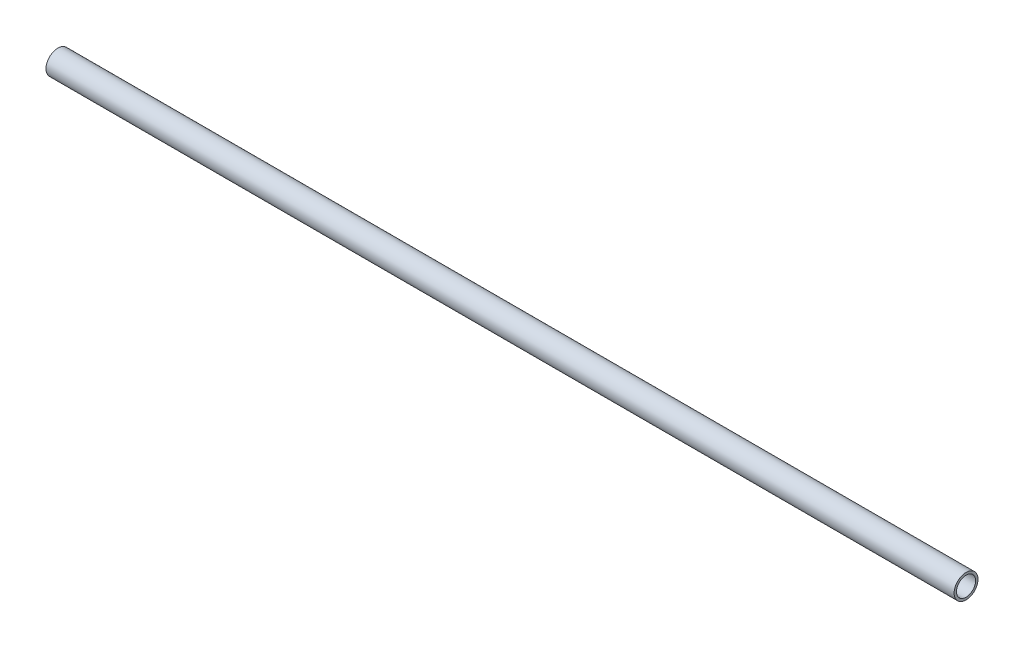
SolidWorks part; units mm, degrees
ref_plane "Front Plane" through (0, 0, 0) normal (0, 0, 1) x (1, 0, 0)
ref_plane "Top Plane" through (0, 0, 0) normal (0, 1, 0) x (1, 0, 0)
ref_plane "Right Plane" through (0, 0, 0) normal (1, 0, 0) x (0, 0, -1)
sketch "Sketch1" plane through (0, 0, 0) normal (0, 1, 0) x (1, 0, 0)
  line L0 (0, 0) -> (640, 0) construction
  line L1 (0, 0) -> (591.2829, 244.9174)
  line L2 (0, 0) -> (591.2829, -244.9174)
  line L3 (0, 0) -> (244.9174, -591.2829)
  line L4 (0, 0) -> (-244.9174, -591.2829)
  line L5 (0, 0) -> (-591.2829, -244.9174)
  line L6 (0, 0) -> (-591.2829, 244.9174)
  line L7 (0, 0) -> (-244.9174, 591.2829)
  line L8 (0, 0) -> (244.9174, 591.2829)
  line L9 (0, 145) -> (55, 145) construction
  line L10 (0, 0) -> (100, 0) construction
  line L11 (0, 0) -> (0, 145) construction
  line L14 (100, 0) -> (100, 145) construction
  circle A0 centre (0, 0) radius 640 construction
  point P15 (0, 0)
  dimension "D1" = 1280
  dimension "D2" = 22.5
  dimension "D4" = 145
  dimension "D5" = 100
  dimension "D6" = 55
  dimension "D3" = 8
sketch "Sketch2" plane through (0, 0, 0) normal (0, 1, 0) x (1, 0, 0)
  line L0 (-486.9956, 169.5033) -> (-66.9956, 169.5033) construction
  line L1 (-188.7141, -86.1278) -> (-188.7141, 241.8722) construction
  line L2 (525.6625, -1048.8053) -> (466.9027, -726.1115) construction
sketch "Sketch3" plane through (0, 0, 0) normal (0, 1, 0) x (1, 0, 0)
  line L0 (0, 0) -> (381.2468, 0) construction
  line L5 (0, 0) -> (0, 199.4415) construction
  line L6 (-10.2736, 158.9263) -> (10.2736, 158.9263)
  line L7 (10.2736, 158.9263) -> (13.1995, 163.9003)
  line L8 (13.1995, 163.9003) -> (45.5131, 148.2994)
  line L9 (45.5131, 148.2994) -> (66.2904, 80.9335)
  line L10 (66.2904, 80.9335) -> (73.8622, 80.9335)
  line L11 (73.8622, 80.9335) -> (86.8684, 42.4396)
  line L12 (86.8684, 42.4396) -> (86.8684, 30.0712)
  line L13 (86.8684, 30.0712) -> (81.3965, 24.5993)
  line L14 (81.3965, 24.5993) -> (81.3965, -24.5993)
  line L15 (-5.8349, 67.4929) -> (5.8349, 67.4929) construction
  line L16 (16.6008, 64.1674) -> (16.6008, 27.6557) construction
  line L17 (16.6008, 27.6557) -> (13.2646, 22.809) construction
  line L18 (13.2646, 22.809) -> (13.2646, -22.809) construction
  line L19 (5.8349, 128.0146) -> (5.8349, 107.4452)
  line L22 (5.8349, 107.4452) -> (9.2702, 107.4452)
  line L25 (9.2702, 107.4452) -> (10.663, 103.7163)
  line L26 (10.663, 103.7163) -> (20.7578, 101.0699)
  line L27 (20.7578, 101.0699) -> (32.199, 111.7601)
  line L28 (32.199, 111.7601) -> (32.199, 123.5038)
  line L29 (32.199, 123.5038) -> (24.9078, 123.5038)
  line L30 (24.9078, 123.5038) -> (13.8412, 132.5856)
  line L31 (13.8412, 132.5856) -> (9.2702, 132.5856)
  line L32 (9.2702, 132.5856) -> (5.8349, 128.0146)
  line L33 (41.9414, 39.7891) -> (51.4866, 54.1602)
  line L34 (51.4866, 54.1602) -> (55.4027, 54.1602)
  line L35 (55.4027, 54.1602) -> (58.1637, 51.3993)
  line L36 (58.1637, 51.3993) -> (58.1637, 43.1872)
  line L37 (58.1637, 43.1872) -> (66.3555, 28.462)
  line L38 (66.3555, 28.462) -> (66.3555, 24.0728)
  line L39 (66.3555, 24.0728) -> (62.2596, 17.9061)
  line L40 (62.2596, 17.9061) -> (47.8497, 18.1669)
  line L41 (47.8497, 18.1669) -> (41.9414, 27.1878)
  line L42 (41.9414, 27.1878) -> (41.9414, 39.7891)
  line L43 (-41.9414, 27.1878) -> (-41.9414, 39.7891)
  line L44 (-47.8497, 18.1669) -> (-41.9414, 27.1878)
  line L45 (-62.2596, 17.9061) -> (-47.8497, 18.1669)
  line L46 (-66.3555, 24.0728) -> (-62.2596, 17.9061)
  line L47 (-66.3555, 28.462) -> (-66.3555, 24.0728)
  line L48 (-58.1637, 43.1872) -> (-66.3555, 28.462)
  line L49 (-58.1637, 51.3993) -> (-58.1637, 43.1872)
  line L50 (-55.4027, 54.1602) -> (-58.1637, 51.3993)
  line L51 (-51.4866, 54.1602) -> (-55.4027, 54.1602)
  line L52 (-41.9414, 39.7891) -> (-51.4866, 54.1602)
  line L53 (-9.2702, 132.5856) -> (-5.8349, 128.0146)
  line L54 (-13.8412, 132.5856) -> (-9.2702, 132.5856)
  line L55 (-24.9078, 123.5038) -> (-13.8412, 132.5856)
  line L56 (-32.199, 123.5038) -> (-24.9078, 123.5038)
  line L57 (-32.199, 111.7601) -> (-32.199, 123.5038)
  line L58 (-20.7578, 101.0699) -> (-32.199, 111.7601)
  line L59 (-10.663, 103.7163) -> (-20.7578, 101.0699)
  line L60 (-9.2702, 107.4452) -> (-10.663, 103.7163)
  line L61 (-5.8349, 107.4452) -> (-9.2702, 107.4452)
  line L62 (-5.8349, 128.0146) -> (-5.8349, 107.4452)
  line L63 (-13.2646, 22.809) -> (-13.2646, -22.809) construction
  line L64 (-16.6008, 27.6557) -> (-13.2646, 22.809) construction
  line L65 (-16.6008, 64.1674) -> (-16.6008, 27.6557) construction
  line L66 (-81.3965, 24.5993) -> (-81.3965, -24.5993)
  line L67 (-86.8684, 30.0712) -> (-81.3965, 24.5993)
  line L68 (-86.8684, 42.4396) -> (-86.8684, 30.0712)
  line L69 (-73.8622, 80.9335) -> (-86.8684, 42.4396)
  line L70 (-66.2904, 80.9335) -> (-73.8622, 80.9335)
  line L71 (-45.5131, 148.2994) -> (-66.2904, 80.9335)
  line L72 (-13.1995, 163.9003) -> (-45.5131, 148.2994)
  line L73 (-10.2736, 158.9263) -> (-13.1995, 163.9003)
  line L74 (-10.2736, -158.9263) -> (-13.1995, -163.9003)
  line L75 (-13.1995, -163.9003) -> (-45.5131, -148.2994)
  line L76 (-45.5131, -148.2994) -> (-66.2904, -80.9335)
  line L77 (-66.2904, -80.9335) -> (-73.8622, -80.9335)
  line L78 (-73.8622, -80.9335) -> (-86.8684, -42.4396)
  line L79 (-86.8684, -42.4396) -> (-86.8684, -30.0712)
  line L80 (-86.8684, -30.0712) -> (-81.3965, -24.5993)
  line L81 (-16.6008, -64.1674) -> (-16.6008, -27.6557) construction
  line L82 (-16.6008, -27.6557) -> (-13.2646, -22.809) construction
  line L83 (-5.8349, -128.0146) -> (-5.8349, -107.4452)
  line L84 (-5.8349, -107.4452) -> (-9.2702, -107.4452)
  line L85 (-9.2702, -107.4452) -> (-10.663, -103.7163)
  line L86 (-10.663, -103.7163) -> (-20.7578, -101.0699)
  line L87 (-20.7578, -101.0699) -> (-32.199, -111.7601)
  line L88 (-32.199, -111.7601) -> (-32.199, -123.5038)
  line L89 (-32.199, -123.5038) -> (-24.9078, -123.5038)
  line L90 (-24.9078, -123.5038) -> (-13.8412, -132.5856)
  line L91 (-13.8412, -132.5856) -> (-9.2702, -132.5856)
  line L92 (-9.2702, -132.5856) -> (-5.8349, -128.0146)
  line L93 (-41.9414, -39.7891) -> (-51.4866, -54.1602)
  line L94 (-51.4866, -54.1602) -> (-55.4027, -54.1602)
  line L95 (-55.4027, -54.1602) -> (-58.1637, -51.3993)
  line L96 (-58.1637, -51.3993) -> (-58.1637, -43.1872)
  line L97 (-58.1637, -43.1872) -> (-66.3555, -28.462)
  line L98 (-66.3555, -28.462) -> (-66.3555, -24.0728)
  line L99 (-66.3555, -24.0728) -> (-62.2596, -17.9061)
  line L100 (-62.2596, -17.9061) -> (-47.8497, -18.1669)
  line L101 (-47.8497, -18.1669) -> (-41.9414, -27.1878)
  line L102 (-41.9414, -27.1878) -> (-41.9414, -39.7891)
  line L103 (41.9414, -27.1878) -> (41.9414, -39.7891)
  line L104 (47.8497, -18.1669) -> (41.9414, -27.1878)
  line L105 (62.2596, -17.9061) -> (47.8497, -18.1669)
  line L106 (66.3555, -24.0728) -> (62.2596, -17.9061)
  line L107 (66.3555, -28.462) -> (66.3555, -24.0728)
  line L108 (58.1637, -43.1872) -> (66.3555, -28.462)
  line L109 (58.1637, -51.3993) -> (58.1637, -43.1872)
  line L110 (55.4027, -54.1602) -> (58.1637, -51.3993)
  line L111 (51.4866, -54.1602) -> (55.4027, -54.1602)
  line L112 (41.9414, -39.7891) -> (51.4866, -54.1602)
  line L113 (9.2702, -132.5856) -> (5.8349, -128.0146)
  line L114 (13.8412, -132.5856) -> (9.2702, -132.5856)
  line L115 (24.9078, -123.5038) -> (13.8412, -132.5856)
  line L116 (32.199, -123.5038) -> (24.9078, -123.5038)
  line L117 (32.199, -111.7601) -> (32.199, -123.5038)
  line L118 (20.7578, -101.0699) -> (32.199, -111.7601)
  line L119 (10.663, -103.7163) -> (20.7578, -101.0699)
  line L120 (9.2702, -107.4452) -> (10.663, -103.7163)
  line L121 (5.8349, -107.4452) -> (9.2702, -107.4452)
  line L122 (5.8349, -128.0146) -> (5.8349, -107.4452)
  line L123 (16.6008, -27.6557) -> (13.2646, -22.809) construction
  line L124 (16.6008, -64.1674) -> (16.6008, -27.6557) construction
  line L125 (-5.8349, -67.4929) -> (5.8349, -67.4929) construction
  line L126 (86.8684, -30.0712) -> (81.3965, -24.5993)
  line L127 (86.8684, -42.4396) -> (86.8684, -30.0712)
  line L128 (73.8622, -80.9335) -> (86.8684, -42.4396)
  line L129 (66.2904, -80.9335) -> (73.8622, -80.9335)
  line L130 (45.5131, -148.2994) -> (66.2904, -80.9335)
  line L131 (13.1995, -163.9003) -> (45.5131, -148.2994)
  line L132 (10.2736, -158.9263) -> (13.1995, -163.9003)
  line L133 (-10.2736, -158.9263) -> (10.2736, -158.9263)
  line L134 (-5.3457, 68.4929) -> (5.3457, 68.4929)
  line L135 (17.6008, 64.1674) -> (17.6008, 27.3448)
  line L136 (17.6008, 27.3448) -> (14.2646, 22.498)
  line L137 (14.2646, 22.498) -> (14.2646, -22.498)
  line L138 (-17.6008, 64.1674) -> (-17.6008, 27.3448)
  line L139 (-17.6008, 27.3448) -> (-14.2646, 22.498)
  line L140 (-5.3457, 68.4929) -> (5.3457, 68.4929) construction
  line L141 (14.2646, 22.498) -> (14.2646, -22.498) construction
  line L142 (17.6008, -27.3448) -> (14.2646, -22.498) construction
  line L143 (17.6008, -64.1674) -> (17.6008, -27.3448) construction
  line L144 (-14.2646, 22.498) -> (-14.2646, -22.498)
  line L145 (17.6008, -64.1674) -> (17.6008, -27.3448)
  line L146 (17.6008, -27.3448) -> (14.2646, -22.498)
  line L147 (-17.6008, -27.3448) -> (-14.2646, -22.498)
  line L148 (-17.6008, -64.1674) -> (-17.6008, -27.3448)
  line L149 (-5.3457, -68.4929) -> (5.3457, -68.4929)
  arc A0 (5.8349, 67.4929) -> (16.6008, 64.0252) centre (10.663, 64.0364) cw construction
  arc A5 (-5.8349, 67.4929) -> (-16.6008, 64.0252) centre (-10.663, 64.0364) ccw construction
  arc A6 (-5.8349, -67.4929) -> (-16.6008, -64.0252) centre (-10.663, -64.0364) cw construction
  arc A7 (5.8349, -67.4929) -> (16.6008, -64.0252) centre (10.663, -64.0364) ccw construction
  arc A8 (-5.3457, 68.4929) -> (-17.6008, 64.0234) centre (-10.663, 64.0364) ccw
  arc A9 (5.3457, 68.4929) -> (17.6008, 64.0234) centre (10.663, 64.0364) cw
  arc A10 (-5.3457, 68.4929) -> (-17.6008, 64.0234) centre (-10.663, 64.0364) ccw construction
  arc A11 (5.3457, -68.4929) -> (17.6008, -64.0234) centre (10.663, -64.0364) ccw
  arc A12 (-5.3457, -68.4929) -> (-17.6008, -64.0234) centre (-10.663, -64.0364) cw
  ellipse E0 centre (11.3851, 149.6854) end of major axis (12.0553, 155.2702) minor radius 3.0047
  ellipse E1 centre (33.6925, 82.363) end of major axis (41.1096, 88.3895) minor radius 4.3287
  ellipse E2 centre (44.8955, 74.0187) end of major axis (51.4866, 79.374) minor radius 4.6847
  ellipse E3 centre (66.3555, 66.447) end of major axis (67.1471, 72.2416) minor radius 3.5711
  ellipse E4 centre (-66.3555, 66.447) end of major axis (-67.1471, 72.2416) minor radius 3.5711
  ellipse E5 centre (-44.8955, 74.0187) end of major axis (-51.4866, 79.374) minor radius 4.6847
  ellipse E6 centre (-33.6925, 82.363) end of major axis (-41.1096, 88.3895) minor radius 4.3287
  ellipse E7 centre (-11.3851, 149.6854) end of major axis (-12.0553, 155.2702) minor radius 3.0047
  ellipse E8 centre (-11.3851, -149.6854) end of major axis (-12.0553, -155.2702) minor radius 3.0047
  ellipse E9 centre (-33.6925, -82.363) end of major axis (-41.1096, -88.3895) minor radius 4.3287
  ellipse E10 centre (-44.8955, -74.0187) end of major axis (-51.4866, -79.374) minor radius 4.6847
  ellipse E11 centre (-66.3555, -66.447) end of major axis (-67.1471, -72.2416) minor radius 3.5711
  ellipse E12 centre (66.3555, -66.447) end of major axis (67.1471, -72.2416) minor radius 3.5711
  ellipse E13 centre (44.8955, -74.0187) end of major axis (51.4866, -79.374) minor radius 4.6847
  ellipse E14 centre (33.6925, -82.363) end of major axis (41.1096, -88.3895) minor radius 4.3287
  ellipse E15 centre (11.3851, -149.6854) end of major axis (12.0553, -155.2702) minor radius 3.0047
  point P117 (0, 67.4929)
  point P126 (0, 158.9263)
  point P180 (0, -158.9263)
  point P181 (0, -67.4929)
  point P190 (-81.3965, 0)
  point P193 (-13.2646, 0)
  point P234 (13.2646, 0)
  point P237 (81.3965, 0)
  point P261 (0, 68.4929)
  point P271 (14.2646, 0)
  point P274 (-14.2646, 0)
  dimension "D1" = 1
sketch "Sketch4" plane through (0, 0, 0) normal (0, 1, 0) x (1, 0, 0)
  line L0 (0, 0) -> (81.2255, 0) construction
  line L1 (0, 0) -> (0, 97.3086) construction
  line L2 (0, 0) -> (0, 199.4415) construction
  line L3 (-10.1399, 86.6928) -> (10.1399, 86.6928)
  line L4 (10.1399, 86.6928) -> (16.0235, 80.8091)
  line L5 (16.0235, 80.8091) -> (23.9736, 57.3032)
  line L6 (23.9736, 57.3032) -> (23.9736, 47.8894)
  line L7 (23.9736, 47.8894) -> (21.6776, 47.8894)
  line L8 (21.6776, 47.8894) -> (21.6776, 27.2256)
  line L9 (21.6776, 27.2256) -> (27.5382, 22.1416)
  line L10 (27.5382, 22.1416) -> (27.5382, 14.9676)
  line L11 (27.5382, 14.9676) -> (23.9736, 10.8585)
  line L12 (23.9736, 10.8585) -> (23.9736, -10.8585)
  line L13 (-23.9736, 10.8585) -> (-23.9736, -10.8585)
  line L14 (-27.5382, 14.9676) -> (-23.9736, 10.8585)
  line L15 (-27.5382, 22.1416) -> (-27.5382, 14.9676)
  line L16 (-21.6776, 27.2256) -> (-27.5382, 22.1416)
  line L17 (-21.6776, 47.8894) -> (-21.6776, 27.2256)
  line L18 (-23.9736, 47.8894) -> (-21.6776, 47.8894)
  line L19 (-23.9736, 57.3032) -> (-23.9736, 47.8894)
  line L20 (-16.0235, 80.8091) -> (-23.9736, 57.3032)
  line L21 (-10.1399, 86.6928) -> (-16.0235, 80.8091)
  line L22 (-10.1399, -86.6928) -> (-16.0235, -80.8091)
  line L23 (-16.0235, -80.8091) -> (-23.9736, -57.3032)
  line L24 (-23.9736, -57.3032) -> (-23.9736, -47.8894)
  line L25 (-23.9736, -47.8894) -> (-21.6776, -47.8894)
  line L26 (-21.6776, -47.8894) -> (-21.6776, -27.2256)
  line L27 (-21.6776, -27.2256) -> (-27.5382, -22.1416)
  line L28 (-27.5382, -22.1416) -> (-27.5382, -14.9676)
  line L29 (-27.5382, -14.9676) -> (-23.9736, -10.8585)
  line L30 (27.5382, -14.9676) -> (23.9736, -10.8585)
  line L31 (27.5382, -22.1416) -> (27.5382, -14.9676)
  line L32 (21.6776, -27.2256) -> (27.5382, -22.1416)
  line L33 (21.6776, -47.8894) -> (21.6776, -27.2256)
  line L34 (23.9736, -47.8894) -> (21.6776, -47.8894)
  line L35 (23.9736, -57.3032) -> (23.9736, -47.8894)
  line L36 (16.0235, -80.8091) -> (23.9736, -57.3032)
  line L37 (10.1399, -86.6928) -> (16.0235, -80.8091)
  line L38 (-10.1399, -86.6928) -> (10.1399, -86.6928)
  point P3 (0, -86.6928)
  point P27 (0, 86.6928)
  point P37 (-23.9736, 0)
  point P38 (23.9736, 0)
sketch "Sketch5" plane through (0, 0, 0) normal (0, 1, 0) x (1, 0, 0)
  line L0 (0, 68.4929) -> (0, 86.6928) construction
  line L1 (15.4511, 110) -> (223.3697, 546.0887)
  line L2 (0, 0) -> (0, 251.8084) construction
  line L3 (0, 110) -> (47.9221, 110) construction
  line L5 (244.9174, 616.9519) -> (262.4572, 609.0616) construction
  line L6 (262.4572, 609.0616) -> (269.1565, 599.6825) construction
  line L7 (269.1565, 599.6825) -> (256.4381, 571.4103) construction
  line L8 (256.4381, 571.4103) -> (244.9174, 563.1812) construction
  line L9 (244.9174, 563.1812) -> (221.08, 517.0826) construction
  line L10 (221.08, 517.0826) -> (201.6817, 527.1134) construction
  line L11 (201.6817, 527.1134) -> (221.6088, 571.4103) construction
  line L12 (221.6088, 571.4103) -> (218.2415, 584.6462) construction
  line L13 (218.2415, 584.6462) -> (232.4366, 616.2011) construction
  line L14 (232.4366, 616.2011) -> (244.9174, 616.9519) construction
  line L15 (244.9174, 591.2829) -> (309.3694, 564.586) construction
  line L16 (269.6266, 526.9284) -> (173.6132, 566.6985) construction
  line L18 (0, 0) -> (107.3069, 0) construction
  dimension "D1" = 110
  dimension "D2" = 50
sketch "Sketch6" plane through (0, 0, 0) normal (0, 1, 0) x (1, 0, 0)
  line L1 (27.9119, 24.7148) -> (544.6401, 226.6863)
  circle A0 centre (0, 0) radius 640 construction
  circle A1 centre (0, 0) radius 640 construction
  circle A3 centre (0, 0) radius 589.9318 construction
  dimension "D1" = 50.0682
sketch "Sketch19" plane through (0, 0, 0) normal (0, 1, 0) x (1, 0, 0)
  line L0 (128.4599, 309.2664) -> (271.805, 137.4916)
  line L5 (26.7343, 104.6204) -> (234.6528, 540.7091)
  line L6 (26.7343, 104.6204) -> (234.6528, 540.7091) construction
  line L7 (4.1679, 115.3796) -> (212.0865, 551.4683)
  line L8 (4.1679, 115.3796) -> (212.0865, 551.4683) construction
  line L9 (20.631, 43.3425) -> (537.3592, 245.3139)
  line L10 (32.4624, 13.0726) -> (549.1907, 215.044)
  line L11 (32.4624, 13.0726) -> (549.1907, 215.044) construction
  line L12 (23.3613, 36.3571) -> (540.0895, 238.3286)
  line L13 (23.3613, 36.3571) -> (540.0895, 238.3286) construction
  line L14 (20.631, 43.3425) -> (537.3592, 245.3139) construction
  line L15 (30.1192, 103.0065) -> (238.0378, 539.0952)
  line L16 (30.1192, 103.0065) -> (238.0378, 539.0952) construction
  line L22 (21.9961, 39.8498) -> (538.7244, 241.8213)
  line L23 (21.9961, 39.8498) -> (538.7244, 241.8213) construction
  line L24 (33.5042, 101.3926) -> (241.4227, 537.4813)
  line L25 (33.5042, 101.3926) -> (241.4227, 537.4813) construction
  dimension "D1" = 12.5
  dimension "D2" = 12.5
  dimension "D3" = 12.5
  dimension "D4" = 12.5
  dimension "D5" = 16.25
  dimension "D8" = 16.25
  dimension "D10" = 20
  dimension "D11" = 20
sketch "Sketch31" plane through (0, 0, 0) normal (0, 1, 0) x (1, 0, 0)
  line L0 (15.4511, 110) -> (223.3697, 546.0887) construction
  line L1 (27.9119, 24.7148) -> (544.6401, 226.6863) construction
  line L2 (15.4511, 110) -> (223.3697, 546.0887)
  line L3 (27.9119, 24.7148) -> (544.6401, 226.6863)
  line L4 (0, 0) -> (341.2388, 0) construction
  line L5 (0, 0) -> (0, 243.9729) construction
  line L6 (0, 0) -> (0, 251.8084) construction
  line L7 (128.4599, 309.2664) -> (271.805, 137.4916) construction
  line L8 (128.4599, 309.2664) -> (271.805, 137.4916)
  line L9 (27.9119, -24.7148) -> (544.6401, -226.6863)
  line L10 (128.4599, -309.2664) -> (271.805, -137.4916)
  line L11 (15.4511, -110) -> (223.3697, -546.0887)
  line L12 (-15.4511, 110) -> (-223.3697, 546.0887)
  line L13 (-128.4599, 309.2664) -> (-271.805, 137.4916)
  line L14 (-27.9119, 24.7148) -> (-544.6401, 226.6863)
  line L15 (-15.4511, -110) -> (-223.3697, -546.0887)
  line L16 (-128.4599, -309.2664) -> (-271.805, -137.4916)
  line L17 (-27.9119, -24.7148) -> (-544.6401, -226.6863)
  line L19 (-200.1324, -223.379) -> (200.1324, -223.379)
  line L20 (-200.1324, -223.379) -> (-200.1324, 223.379)
  line L21 (-200.1324, 223.379) -> (200.1324, 223.379)
  line L22 (200.1324, -223.379) -> (200.1324, 223.379)
sketch "Sketch32" plane through (0, 0, 0) normal (0, 1, 0) x (1, 0, 0)
  line L1 (-200.1324, -223.379) -> (200.1324, -223.379) construction
  line L2 (-190.1324, -223.379) -> (190.1324, -223.379)
  line L3 (-200.1324, -316.7325) -> (-200.1324, -130.0255) construction
  line L4 (200.1324, -316.7325) -> (200.1324, -130.0255) construction
  line L5 (-190.1324, -316.7325) -> (-190.1324, -130.0255) construction
  line L6 (190.1324, -316.7325) -> (190.1324, -130.0255) construction
  point P5 (-200.1324, -223.379)
  point P8 (200.1324, -223.379)
  dimension "D1" = 10
  dimension "D2" = 10
sweep "Sweep1" add path "Sketch32" circular profile diameter 10 parameters "D3"=10
sweep "Cut-Sweep1" cut path "Sketch32<3>" circular profile diameter 8 parameters "D3"=8
sketch "Sketch32<3>" plane through (0, 0, 0) normal (0, 1, 0) x (1, 0, 0) same geometry as "Sketch32"
